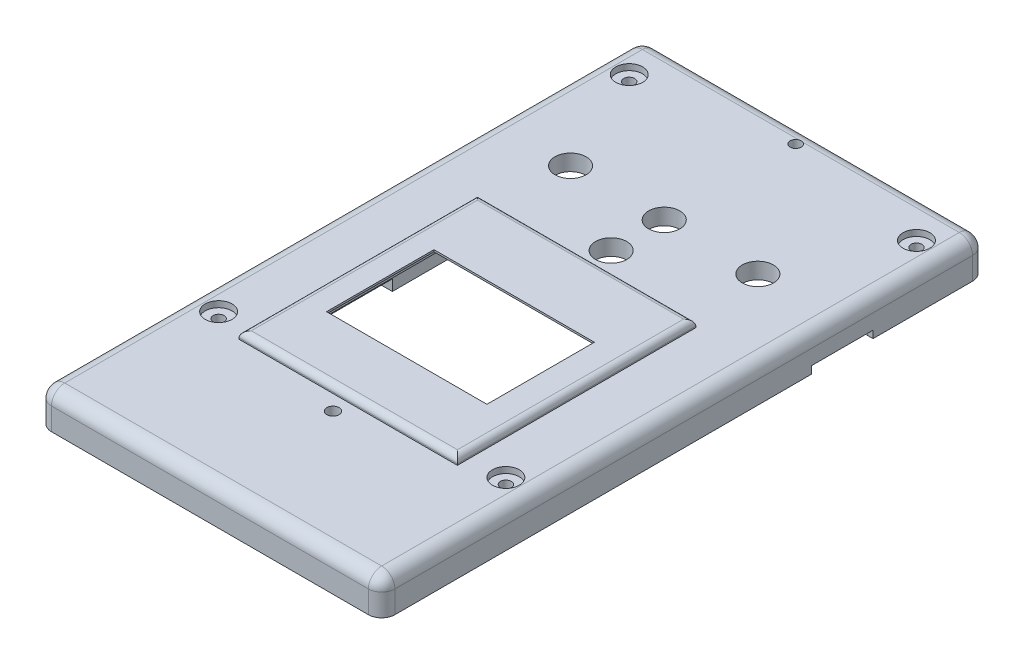
SolidWorks part; units mm, degrees
ref_plane "Face" through (0, 0, 0) normal (0, 0, 1) x (1, 0, 0)
ref_plane "Dessus" through (0, 0, 0) normal (0, 1, 0) x (1, 0, 0)
ref_plane "Droite" through (0, 0, 0) normal (1, 0, 0) x (0, 0, -1)
sketch "Sketch1" plane through (0, 0, 0) normal (0, 1, 0) x (1, 0, 0)
  line L0 (0, -49.53) -> (0, 0) construction
  line L1 (27.94, -49.53) -> (-27.94, -49.53)
  line L2 (27.94, -49.53) -> (27.94, 48.768)
  line L3 (27.94, 48.768) -> (-27.94, 48.768)
  line L4 (-27.94, -49.53) -> (-27.94, 48.768)
  point P0 (0, 0)
  dimension "D1" = 55.88
  dimension "D2" = 49.53
  dimension "D3" = 48.768
extrude "Boss-Extrude1" add sketch "Sketch1" along normal blind 4.99
fillet "Fillet1" radius 2.159 8 edges at (0, 4.99, 49.53) (27.94, 4.99, 0.381) (0, 4.99, -48.768) (-27.94, 4.99, 0.381) (-27.94, 2.495, -48.768) (27.94, 2.495, -48.768) (27.94, 2.495, 49.53) (-27.94, 2.495, 49.53)
sketch "Sketch3" plane through (0, 0, 0) normal (0, -1, 0) x (1, 0, 0)
  line L1 (21.6281, -38.862) -> (-20.4089, -38.862)
  line L2 (21.6281, -38.862) -> (21.6281, 26.576)
  line L3 (21.6281, 26.576) -> (-20.4089, 26.576)
  line L4 (-20.4089, -38.862) -> (-20.4089, 26.576)
  line L5 (21.6281, -38.862) -> (-20.4089, 26.576) construction
  line L6 (21.6281, 26.576) -> (-20.4089, -38.862) construction
  point P0 (0.6096, -6.143)
  dimension "D1" = 42.037
  dimension "D2" = 26.576
  dimension "D3" = 38.862
  dimension "D4" = 0.6096
sketch "Sketch7" plane through (0, 0, 0) normal (0, -1, 0) x (1, 0, 0)
  line L6 (-25.781, -47.752) -> (25.781, -47.752)
  line L9 (26.924, 47.371) -> (26.924, -46.609)
  line L10 (-26.924, -46.609) -> (-26.924, 47.371)
  line L11 (-25.781, 48.514) -> (25.781, 48.514)
  line L12 (26.924, 47.371) -> (26.924, -46.609)
  line L13 (-26.924, -46.609) -> (-26.924, 47.371)
  line L14 (-25.781, 48.514) -> (25.781, 48.514)
  arc A9 (25.781, -47.752) -> (26.924, -46.609) centre (25.781, -46.609) ccw
  arc A16 (25.781, -47.752) -> (26.924, -46.609) centre (25.781, -46.609) ccw
  arc A17 (-26.924, -46.609) -> (-25.781, -47.752) centre (-25.781, -46.609) ccw
  arc A18 (-26.924, -46.609) -> (-25.781, -47.752) centre (-25.781, -46.609) ccw
  arc A19 (-25.781, 48.514) -> (-26.924, 47.371) centre (-25.781, 47.371) ccw
  arc A20 (-25.781, 48.514) -> (-26.924, 47.371) centre (-25.781, 47.371) ccw
  arc A21 (26.924, 47.371) -> (25.781, 48.514) centre (25.781, 47.371) ccw
  arc A22 (26.924, 47.371) -> (25.781, 48.514) centre (25.781, 47.371) ccw
  dimension "D1" = 1.016
  dimension "D2" = 1.016
extrude "Cut-Extrude4" cut sketch "Sketch7" against normal blind 0.5874
sketch "Sketch8" plane through (0, 0, 0) normal (0, -1, 0) x (1, 0, 0)
  line L0 (27.94, 47.371) -> (27.94, -46.609) construction
  line L2 (26.924, -46.609) -> (26.924, 47.371) construction
  line L3 (-25.781, -47.752) -> (25.781, -47.752) construction
  line L4 (26.924, -46.609) -> (26.924, -40.386)
  line L5 (21.717, -47.752) -> (25.781, -47.752)
  line L6 (21.717, -47.752) -> (21.717, -40.386)
  line L7 (21.717, -40.386) -> (26.924, -40.386)
  circle A0 centre (23.4188, -43.006) radius 0.889
  arc A1 (25.781, -47.752) -> (26.924, -46.609) centre (25.781, -46.609) ccw construction
  arc A2 (25.781, -47.752) -> (26.924, -46.609) centre (25.781, -46.609) ccw
  dimension "D3" = 1.778
  dimension "D1" = 4.5212
  dimension "D2" = 43.006
  dimension "D4" = 6.223
  dimension "D5" = 40.386
sketch "Sketch9" plane through (0, 0, 0) normal (0, -1, 0) x (1, 0, 0)
  line L0 (-26.924, 47.371) -> (-26.924, -46.609) construction
  line L1 (-25.781, -47.752) -> (25.781, -47.752) construction
  line L2 (-26.924, -40.005) -> (-26.924, -46.609)
  line L3 (-25.781, -47.752) -> (-20.447, -47.752)
  line L4 (-20.447, -47.752) -> (-20.447, -40.005)
  line L5 (-20.447, -40.005) -> (-26.924, -40.005)
  line L6 (-27.94, -46.609) -> (-27.94, 47.371) construction
  arc A0 (-26.924, -46.609) -> (-25.781, -47.752) centre (-25.781, -46.609) ccw construction
  arc A1 (-26.924, -46.609) -> (-25.781, -47.752) centre (-25.781, -46.609) ccw
  circle A2 centre (-23.3172, -43.006) radius 0.889
  dimension "D5" = 1.778
  dimension "D1" = 7.493
  dimension "D2" = 43.006
  dimension "D3" = 3.6068
  dimension "D4" = 40.005
sketch "Sketch10" plane through (0, 0, 0) normal (0, -1, 0) x (1, 0, 0)
  line L0 (-27.94, -46.609) -> (-27.94, 47.371) construction
  line L1 (-26.924, 47.371) -> (-26.924, -46.609) construction
  line L2 (-26.924, 17.78) -> (-20.447, 17.78)
  line L3 (-26.924, 17.78) -> (-26.924, 26.67)
  line L4 (-26.924, 26.67) -> (-20.447, 26.67)
  line L5 (-20.447, 17.78) -> (-20.447, 26.67)
  circle A0 centre (-23.3172, 23.796) radius 0.889
  dimension "D6" = 1.778
  dimension "D1" = 4.6228
  dimension "D2" = 23.796
  dimension "D3" = 6.477
  dimension "D4" = 26.67
  dimension "D5" = 17.78
sketch "Sketch11" plane through (0, 0, 0) normal (0, -1, 0) x (1, 0, 0)
  line L0 (26.924, -46.609) -> (26.924, 47.371) construction
  line L1 (26.924, 27.686) -> (21.7502, 27.686)
  line L2 (26.924, 27.686) -> (26.924, 20.32)
  line L3 (26.924, 20.32) -> (21.7502, 20.32)
  line L4 (21.7502, 27.686) -> (21.7502, 20.32)
  circle A0 centre (23.4188, 23.796) radius 0.889
  dimension "D6" = 1.778
  dimension "D1" = 23.796
  dimension "D2" = 23.4188
  dimension "D3" = 27.686
  dimension "D4" = 20.32
  dimension "D5" = 21.7502
sketch "Sketch12" plane through (0, 0.5874, 0) normal (0, -1, 0) x (1, 0, 0)
  line L0 (26.924, -38.1) -> (19.812, -38.1)
  line L1 (-26.924, 27.94) -> (-16.28, 27.94)
  line L3 (-26.924, 13.7274) -> (-16.28, 13.7274)
  line L4 (26.924, -46.609) -> (26.924, 47.371)
  line L5 (25.781, 48.514) -> (-25.781, 48.514)
  line L6 (-26.924, 47.371) -> (-26.924, -46.609)
  line L7 (-25.781, -47.752) -> (25.781, -47.752)
  line L8 (26.924, -38.1) -> (26.924, -17.145)
  line L9 (25.781, 48.514) -> (8.5725, 48.514)
  line L10 (-26.924, 47.371) -> (-26.924, 27.94)
  line L11 (-19.812, -47.752) -> (19.812, -47.752)
  line L12 (-16.28, 27.94) -> (-16.28, 13.7274)
  line L13 (26.924, 27.94) -> (19.812, 27.94)
  line L17 (19.812, -38.1) -> (19.812, -47.752)
  line L18 (-26.924, -38.1) -> (-19.812, -38.1)
  line L19 (-19.812, -38.1) -> (-19.812, -47.752)
  line L20 (-26.924, 3.429) -> (-16.28, 3.429)
  line L21 (-16.28, 3.429) -> (-16.28, -17.145)
  line L22 (-16.28, -17.145) -> (-26.924, -17.145)
  line L25 (19.812, -17.145) -> (26.924, -17.145)
  line L26 (0, 44.704) -> (0, 0) construction
  line L28 (8.5725, 48.514) -> (8.5725, 44.704)
  line L29 (8.5725, 44.704) -> (-8.5725, 44.704)
  line L30 (-8.5725, 48.514) -> (-8.5725, 44.704)
  line L31 (0, 0) -> (0, -47.752) construction
  line L36 (-8.5725, 48.514) -> (-25.781, 48.514)
  line L37 (26.924, 27.94) -> (26.924, 47.371)
  line L38 (-26.924, 13.7274) -> (-26.924, 3.429)
  line L39 (-26.924, -17.145) -> (-26.924, -38.1)
  line L40 (26.924, -3.275) -> (26.924, 12.725)
  line L41 (19.812, -17.145) -> (19.812, -11.275)
  line L42 (19.812, -11.275) -> (22.346, -11.275)
  line L43 (22.346, -11.275) -> (22.346, -3.275)
  line L44 (22.346, -3.275) -> (26.924, -3.275)
  line L45 (19.812, 27.94) -> (19.812, 20.725)
  line L46 (19.812, 20.725) -> (22.346, 20.725)
  line L47 (22.346, 20.725) -> (22.346, 12.725)
  line L48 (22.346, 12.725) -> (26.924, 12.725)
  arc A4 (25.781, -47.752) -> (26.924, -46.609) centre (25.781, -46.609) ccw
  arc A5 (26.924, 47.371) -> (25.781, 48.514) centre (25.781, 47.371) ccw
  arc A6 (-25.781, 48.514) -> (-26.924, 47.371) centre (-25.781, 47.371) ccw
  arc A7 (-26.924, -46.609) -> (-25.781, -47.752) centre (-25.781, -46.609) ccw
  arc A9 (26.924, 47.371) -> (25.781, 48.514) centre (25.781, 47.371) ccw
  arc A10 (-25.781, 48.514) -> (-26.924, 47.371) centre (-25.781, 47.371) ccw
  dimension "D2" = 12.725
  dimension "D3" = 17.145
  dimension "D4" = 3.81
  dimension "D5" = 27.94
  dimension "D6" = 14.2126
  dimension "D7" = 3.429
  dimension "D8" = 17.145
  dimension "D9" = 38.1
  dimension "D10" = 39.624
  dimension "D11" = 16.28
  dimension "D12" = 4.578
  dimension "D13" = 32
  dimension "D14" = 20.725
  dimension "D15" = 16
  dimension "D1" = 0
extrude "Cut-Extrude5" cut sketch "Sketch12" against normal blind 1.778
fillet "Fillet4" radius 1.016 11 edges at (17.1767, 2.3654, 48.514) (26.5892, 2.3654, 48.1792) (26.924, 2.3654, 37.6555) (26.924, 2.3654, 4.725) (26.924, 2.3654, -27.6225) (0, 2.3654, -47.752) (-26.924, 2.3654, -27.6225) (-26.924, 2.3654, 8.5782) (-26.924, 2.3654, 37.6555) (-26.5892, 2.3654, 48.1792) (-17.1767, 2.3654, 48.514)
hole_wizard "Chambrage pour vis à tête ronde à 6 pans creux #11" positions "Sketch13" profile "Sketch14" counterbore size "#1" standard "Ansi Inch"
sketch "Sketch13" plane through (0, 4.99, 0) normal (0, 1, 0) x (1, 0, 0)
  point P0 (-23.3172, -24.796)
  point P3 (23.4188, -24.796)
  point P6 (23.4188, 42.006)
  point P9 (-23.3172, 42.006)
sketch "Sketch14" plane through (-23.3172, 4.99, 24.796) normal (1, 0, 0) x (0, 0, 1)
  line L0 (0, 0) -> (0, 6.5342)
  line L1 (0, 6.5342) -> (0.889, 6)
  line L2 (0.889, 6) -> (0.889, 0.9906)
  line L3 (0.889, 0.9906) -> (2.1844, 0.9906)
  line L4 (2.1844, 0.9906) -> (2.1844, 0)
  line L5 (2.1844, 0) -> (0, 0)
  line L10 (0, 6.5342) -> (-0.889, 6) construction
  line L11 (0, -6.35) -> (0, 107.95) construction
  dimension "Diamètre du perçage" = 1.778
  dimension "Profondeur du perçage" = 6
  dimension "Diamètre du chambrage" = 4.3688
  dimension "Profondeur du chambrage" = 0.9906
  dimension "Angle de pointe" = 118
sketch "Sketch15" plane through (0, 2.3654, 0) normal (0, -1, 0) x (1, 0, 0)
  line L0 (0, 0) -> (0, -15.748) construction
  line L1 (0, -15.748) -> (0, -24.384) construction
  line L2 (0, -24.384) -> (-15.24, -24.384) construction
  line L3 (0, -24.384) -> (15.24, -24.384) construction
  circle A0 centre (0, -24.384) radius 2.54
  circle A1 centre (-15.24, -24.384) radius 2.54
  circle A2 centre (15.24, -24.384) radius 2.54
  circle A3 centre (0, -15.748) radius 2.54
  dimension "D4" = 5.08
  dimension "D1" = 24.384
  dimension "D2" = 15.748
  dimension "D3" = 30.48
extrude "Cut-Extrude6" cut sketch "Sketch15" against normal through all
sketch "Sketch16" plane through (0, 0.5874, 0) normal (0, 1, 0) x (1, 0, 0)
  line L0 (-25.781, -48.514) -> (-8.5725, -48.514) construction
  line L1 (16.424, -25.764) -> (-16.424, -25.764)
  line L2 (16.424, -25.764) -> (16.424, 11.236)
  line L3 (16.424, 11.236) -> (-16.424, 11.236)
  line L4 (-16.424, -25.764) -> (-16.424, 11.236)
  line L5 (26.924, 46.609) -> (26.924, -47.371) construction
  point P9 (0, 11.236)
  dimension "D1" = 22.75
  dimension "D2" = 10.5
  dimension "D3" = 37
extrude "Cut-Extrude7" cut sketch "Sketch16" along normal blind 4.2
sketch "Sketch17" plane through (0, 0, 0) normal (0, -1, 0) x (1, 0, 0)
  line L0 (-25.781, -47.752) -> (25.781, -47.752) construction
  line L1 (26.924, -46.609) -> (26.924, 47.371) construction
  line L2 (25.781, 48.514) -> (-25.781, 48.514) construction
  line L3 (-26.924, 47.371) -> (-26.924, -46.609) construction
  line L4 (-27.94, 47.371) -> (-27.94, -46.609)
  line L5 (-25.781, -48.768) -> (25.781, -48.768)
  line L6 (27.94, -46.609) -> (27.94, 47.371)
  line L7 (25.781, 49.53) -> (-25.781, 49.53)
  line L8 (-27.94, 47.371) -> (-27.94, -46.609)
  line L9 (-25.781, -48.768) -> (25.781, -48.768)
  line L10 (27.94, -46.609) -> (27.94, 47.371)
  line L11 (25.781, 49.53) -> (-25.781, 49.53)
  line L12 (-25.781, -47.752) -> (25.781, -47.752)
  line L13 (26.924, -46.609) -> (26.924, 47.371)
  line L14 (25.781, 48.514) -> (-25.781, 48.514)
  line L15 (-26.924, 47.371) -> (-26.924, -46.609)
  arc A0 (-26.924, -46.609) -> (-25.781, -47.752) centre (-25.781, -46.609) ccw construction
  arc A1 (25.781, -47.752) -> (26.924, -46.609) centre (25.781, -46.609) ccw construction
  arc A2 (26.924, 47.371) -> (25.781, 48.514) centre (25.781, 47.371) ccw construction
  arc A3 (-25.781, 48.514) -> (-26.924, 47.371) centre (-25.781, 47.371) ccw construction
  arc A4 (-27.94, -46.609) -> (-25.781, -48.768) centre (-25.781, -46.609) ccw
  arc A5 (25.781, -48.768) -> (27.94, -46.609) centre (25.781, -46.609) ccw
  arc A6 (27.94, 47.371) -> (25.781, 49.53) centre (25.781, 47.371) ccw
  arc A7 (-25.781, 49.53) -> (-27.94, 47.371) centre (-25.781, 47.371) ccw
  arc A8 (-27.94, -46.609) -> (-25.781, -48.768) centre (-25.781, -46.609) ccw
  arc A9 (25.781, -48.768) -> (27.94, -46.609) centre (25.781, -46.609) ccw
  arc A10 (27.94, 47.371) -> (25.781, 49.53) centre (25.781, 47.371) ccw
  arc A11 (-25.781, 49.53) -> (-27.94, 47.371) centre (-25.781, 47.371) ccw
  arc A12 (-26.924, -46.609) -> (-25.781, -47.752) centre (-25.781, -46.609) ccw
  arc A13 (25.781, -47.752) -> (26.924, -46.609) centre (25.781, -46.609) ccw
  arc A14 (26.924, 47.371) -> (25.781, 48.514) centre (25.781, 47.371) ccw
  arc A15 (-25.781, 48.514) -> (-26.924, 47.371) centre (-25.781, 47.371) ccw
  dimension "D1" = 0
extrude "Boss-Extrude2" add sketch "Sketch17" along normal blind 0.8
sketch "Esquisse19" plane through (0, 4.99, 0) normal (0, 1, 0) x (1, 0, 0)
  line L0 (-25.781, 48.768) -> (25.781, 48.768) construction
  line L1 (17.765, 11.768) -> (-17.765, 11.768)
  line L2 (17.765, 11.768) -> (17.765, -27.03)
  line L3 (17.765, -27.03) -> (-17.765, -27.03)
  line L4 (-17.765, 11.768) -> (-17.765, -27.03)
  line L5 (-27.94, -47.371) -> (-27.94, 46.609) construction
  line L6 (27.94, 46.609) -> (27.94, -47.371) construction
  line L7 (25.781, -49.53) -> (-25.781, -49.53) construction
  dimension "D1" = 37
  dimension "D2" = 10.175
  dimension "D3" = 10.175
  dimension "D4" = 22.5
extrude "Boss.-Extru.2" add sketch "Esquisse19" along normal blind 1.2
sketch "Esquisse1" plane through (0, 4.99, 0) normal (0, 1, 0) x (1, 0, 0)
  line L0 (25.781, -48.514) -> (-25.781, -48.514) construction
  circle A0 centre (0, -29.514) radius 1
  dimension "D1" = 19
  dimension "D2" = 2
extrude "Enlèv. mat.-Extru.1" cut sketch "Esquisse1" against normal through all
sketch "Esquisse5" plane through (27.94, 0, 0) normal (1, 0, 0) x (0, 0, -1)
  line L0 (46.609, -0.8) -> (-47.371, -0.8) construction
  line L1 (30.418, -0.8) -> (20.418, -0.8)
  line L2 (30.418, -0.8) -> (30.418, 0.4)
  line L3 (30.418, 0.4) -> (20.418, 0.4)
  line L4 (20.418, -0.8) -> (20.418, 0.4)
  line L5 (48.768, 2.831) -> (48.768, -0.8) construction
  dimension "D1" = 18.35
  dimension "D2" = 10
  dimension "D3" = 1.2
extrude "Enlèv. mat.-Extru.3" cut sketch "Esquisse5" against normal blind 2
sketch "Esquisse13" plane through (0, 4.7874, 0) normal (0, -1, 0) x (1, 0, 0)
  line L0 (16.424, -11.236) -> (16.424, 25.764) construction
  line L1 (-14.124, 23.914) -> (13.624, 23.914)
  line L2 (-14.124, 23.914) -> (-14.124, -7.236)
  line L3 (-14.124, -7.236) -> (13.624, -7.236)
  line L4 (13.624, 23.914) -> (13.624, -7.236)
  line L5 (-16.424, 25.764) -> (16.424, 25.764) construction
  line L8 (-16.28, -11.236) -> (16.424, -11.236) construction
  line L9 (-16.424, -11.236) -> (-16.424, 25.764) construction
  dimension "D1" = 2.8
  dimension "D2" = 2.3
  dimension "D3" = 1.85
  dimension "D4" = 4
extrude "Enlèv. mat.-Extru.6" cut sketch "Esquisse13" against normal blind 1.1
sketch "Esquisse14" plane through (0, 4.99, 0) normal (0, 1, 0) x (1, 0, 0)
  line L4 (25.781, -47.371) -> (25.781, 46.609) construction
  circle A0 centre (0, 45.768) radius 0.9
  dimension "D1" = 1.8
  dimension "D2" = 25.781
extrude "Enlèv. mat.-Extru.7" cut sketch "Esquisse14" against normal blind 10
sketch "Esquisse15" plane through (0, 0, -48.768) normal (0, 0, -1) x (-1, 0, 0)
  line L0 (25.781, -0.8) -> (-25.781, -0.8) construction
  line L1 (19.85, -0.8) -> (7.91, -0.8)
  line L2 (19.85, -0.8) -> (19.85, -0.7)
  line L3 (19.85, -0.7) -> (7.91, -0.7)
  line L4 (7.91, -0.8) -> (7.91, -0.7)
  line L5 (27.94, 2.831) -> (27.94, -0.8) construction
  dimension "D1" = 8.09
  dimension "D2" = 11.94
  dimension "D3" = 0.1
extrude "Enlèv. mat.-Extru.8" cut sketch "Esquisse15" against normal up to next
chamfer "Chanfrein1" distance 1 angle 50 1 edges at (-13.88, -0.7, -48.768) first distance on face at (-6.94, 0.1327, -48.768)
sketch "Esquisse16" plane through (0, 0, -48.768) normal (0, 0, -1) x (-1, 0, 0)
  line L0 (7.91, -0.8) -> (-25.781, -0.8) construction
  line L1 (-18.76, -0.8) -> (-6.95, -0.8)
  line L2 (-18.76, -0.8) -> (-18.76, -0.3)
  line L3 (-18.76, -0.3) -> (-6.95, -0.3)
  line L4 (-6.95, -0.8) -> (-6.95, -0.3)
  line L5 (-27.94, -0.8) -> (-27.94, 2.831) construction
  dimension "D1" = 20.99
  dimension "D2" = 9.18
  dimension "D3" = 0.5
extrude "Enlèv. mat.-Extru.9" cut sketch "Esquisse16" against normal up to next
sketch "Esquisse17" plane through (0, 0, -48.768) normal (0, 0, -1) x (-1, 0, 0)
  line L0 (7.91, -0.8) -> (-6.95, -0.8) construction
  line L1 (-4.5, -0.8) -> (4.5, -0.8)
  line L2 (-4.5, -0.8) -> (-4.5, 0)
  line L3 (-4.5, 0) -> (4.5, 0)
  line L4 (4.5, -0.8) -> (4.5, 0)
  line L5 (-27.94, -0.8) -> (-27.94, 2.831) construction
  line L6 (27.94, 2.831) -> (27.94, -0.8) construction
  dimension "D1" = 23.44
  dimension "D2" = 23.44
  dimension "D3" = 0.8
extrude "Enlèv. mat.-Extru.10" cut sketch "Esquisse17" against normal blind 10
sketch "Esquisse18" plane through (0, 0, -48.768) normal (0, 0, -1) x (-1, 0, 0)
  line L0 (-4.5, -0.8) -> (-5, -0.8)
  line L1 (-4.5, -0.8) -> (-6.95, -0.8) construction
  line L2 (-5, -0.8) -> (-5, 0.5)
  line L3 (-5, 0.5) -> (5, 0.5)
  line L4 (5, 0.5) -> (5, -0.8)
  line L5 (7.91, -0.8) -> (4.5, -0.8) construction
  line L6 (5, -0.8) -> (4.5, -0.8)
  line L7 (4.5, -0.8) -> (4.5, 0)
  line L8 (4.5, 0) -> (-4.5, 0)
  line L9 (-4.5, 0) -> (-4.5, -0.8)
  dimension "D1" = 0.5
  dimension "D2" = 0.5
  dimension "D3" = 0.5
extrude "Boss.-Extru.1" add sketch "Esquisse18" along normal blind 1.1
fillet "Congé1" radius 0.2 3 edges at (5, -0.15, -49.868) (0, 0.5, -49.868) (-5, -0.15, -49.868)
sketch "Esquisse12" plane through (0, 4.7874, 0) normal (0, 1, 0) x (1, 0, 0)
  line L1 (-13.334, 0.256) -> (12.764, 0.256)
  line L2 (-13.334, 0.256) -> (-13.334, -17.224)
  line L3 (-13.334, -17.224) -> (12.764, -17.224)
  line L4 (12.764, 0.256) -> (12.764, -17.224)
  line L8 (-14.124, -23.914) -> (-14.124, 7.236) construction
  line L9 (-14.124, 7.236) -> (13.624, 7.236) construction
  line L10 (13.624, 7.236) -> (13.624, -23.914) construction
  line L11 (13.624, -23.914) -> (-14.124, -23.914) construction
  dimension "D1" = 0.79
  dimension "D2" = 6.98
  dimension "D3" = 6.69
  dimension "D4" = 0.86
extrude "Enlèv. mat.-Extru.5" cut sketch "Esquisse12" along normal blind 22
fillet "Congé2" radius 1 4 edges at (0, 6.19, 27.03) (-17.765, 6.19, 7.631) (0, 6.19, -11.768) (17.765, 6.19, 7.631)
